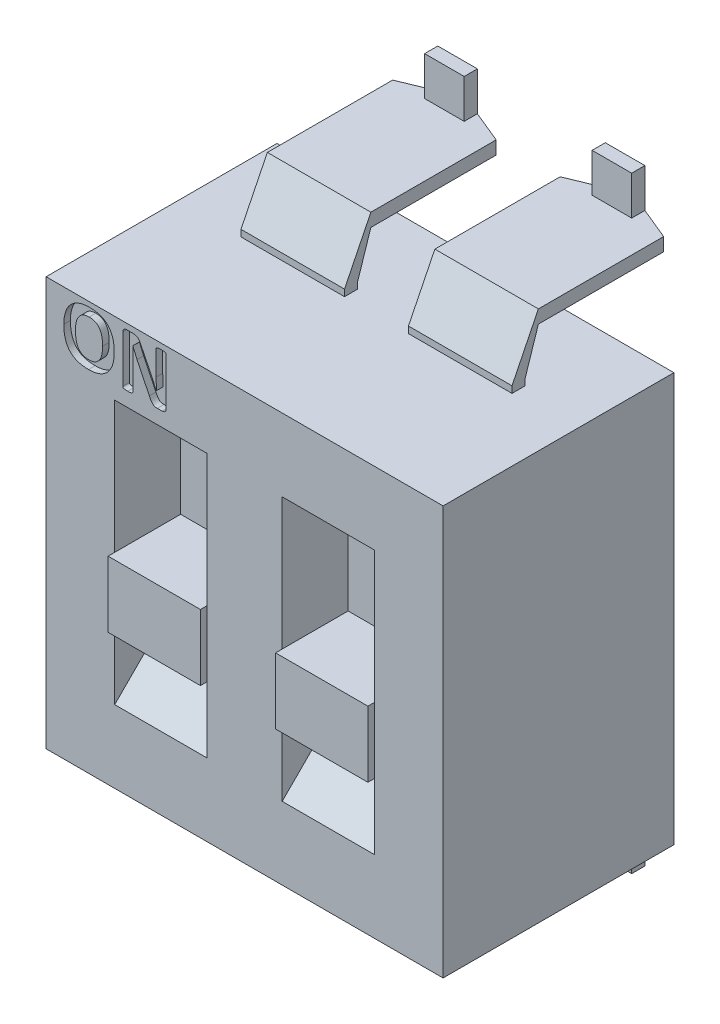
SolidWorks part; units mm, degrees
other "Детальный элемент1"
ref_plane "Спереди" through (0, 0, 0) normal (0, 0, 1) x (1, 0, 0)
ref_plane "Сверху" through (0, 0, 0) normal (0, 1, 0) x (1, 0, 0)
ref_plane "Справа" through (0, 0, 0) normal (1, 0, 0) x (0, 0, -1)
ref_plane "Плоскость1" through (0, 0, 1) normal (0, 0, 1) x (1, 0, 0)
sketch "Эскиз1" plane through (0, 0, 1) normal (0, 0, 1) x (1, 0, 0)
  line L1 (-3.01, -3.1) -> (3.01, -3.1)
  line L2 (-3.01, -3.1) -> (-3.01, 3.1)
  line L3 (-3.01, 3.1) -> (3.01, 3.1)
  line L4 (3.01, -3.1) -> (3.01, 3.1)
  line L5 (-3.01, -3.1) -> (3.01, 3.1) construction
  line L6 (-3.01, 3.1) -> (3.01, -3.1) construction
  point P0 (0, 0)
  dimension "D1" = 6.2
  dimension "D2" = 6.02
extrude "Бобышка-Вытянуть1" add sketch "Эскиз1" along normal blind 3.5
sketch "Эскиз2" plane through (0, -3.1, 0) normal (0, -1, 0) x (1, 0, 0)
  line L0 (-3.01, 1) -> (3.01, 1) construction
  line L1 (-2.055, 2.5) -> (-0.485, 2.5)
  line L2 (-2.055, 2.5) -> (-2.055, 2.3)
  line L3 (-2.055, 2.3) -> (-0.485, 2.3)
  line L4 (-0.485, 2.5) -> (-0.485, 2.3)
  line L5 (-2.055, 2.5) -> (-0.485, 2.3) construction
  line L6 (-2.055, 2.3) -> (-0.485, 2.5) construction
  line L7 (-3.01, 4.5) -> (-3.01, 1) construction
  point P0 (-1.27, 2.4)
  dimension "D1" = 1.57
  dimension "D2" = 0.2
  dimension "D3" = 1.4
  dimension "D4" = 1.74
extrude "Бобышка-Вытянуть2" add sketch "Эскиз2" along normal blind 0.1 separate body
sketch "Эскиз3" plane through (0, 0, 0) normal (0, 0, 1) x (1, 0, 0)
  line L1 (-1.57, -3.81) -> (-0.97, -3.81)
  line L2 (-1.57, -3.81) -> (-1.57, -4.6)
  line L3 (-1.57, -4.6) -> (-0.97, -4.6)
  line L4 (-0.97, -3.81) -> (-0.97, -4.6)
  line L5 (-1.57, -3.81) -> (-0.97, -4.6) construction
  line L6 (-1.57, -4.6) -> (-0.97, -3.81) construction
  point P0 (-1.27, -4.205)
  dimension "D1" = 0.6
  dimension "D2" = 0.79
  dimension "D3" = 4.6
extrude "Бобышка-Вытянуть3" add sketch "Эскиз3" along normal blind 0.2 separate body
sketch "Эскиз4" plane through (0, 0, 0.2) normal (0, 0, 1) x (1, 0, 0)
  line L0 (-0.97, -3.81) -> (-1.57, -3.81) construction
  line L1 (-2.055, -3.81) -> (-0.485, -3.81)
  line L2 (-2.055, -3.81) -> (-2.055, -4.01)
  line L3 (-2.055, -4.01) -> (-0.485, -4.01)
  line L4 (-0.485, -3.81) -> (-0.485, -4.01)
  dimension "D1" = 0.2
extrude "Бобышка-Вытянуть4" add sketch "Эскиз4" along normal offset from surface (1.9 mm away) 0.2 up to face at (-1.27, -3.15, 2.3)
chamfer "Фаска1" distance 0.2 distance2 0.485 2 edges at (-0.97, -3.91, 0.2) (-1.57, -3.91, 0.2) first distance on face at (-0.97, -4.166, 0.12) first distance on face at (-1.57, -4.166, 0.12)
loft "По сечениям1" add section face at (-1.27, -3.2, 2.4) section face at (-1.27, -3.91, 2.1) connector at (-2.055, -3.2, 2.5) connector at (-2.055, -4.01, 2.1)
sketch "Эскиз5" plane through (0, 0, 4.5) normal (0, 0, 1) x (1, 0, 0)
  line L5 (-1.97, 1) -> (-0.57, 1)
  line L6 (-1.97, 1) -> (-1.97, -1)
  line L7 (-1.97, -1) -> (-0.57, -1)
  line L8 (-0.57, 1) -> (-0.57, -1)
  line L9 (-1.97, 1) -> (-0.57, -1) construction
  line L10 (-1.97, -1) -> (-0.57, 1) construction
  point P0 (-1.27, 0)
  dimension "D1" = 2
  dimension "D2" = 1.4
extrude "Вырез-Вытянуть1" cut sketch "Эскиз5" against normal blind 1
chamfer "Фаска2" distance 1 angle 45 2 edges at (-1.27, 1, 4.5) (-1.27, -1, 4.5)
sketch "Эскиз6" plane through (0, 0, 3.5) normal (0, 0, 1) x (1, 0, 0)
  line L0 (-0.57, -1) -> (-0.57, 1) construction
  line L1 (-1.97, -1) -> (-0.57, -1)
  line L2 (-1.97, -1) -> (-1.97, 0)
  line L3 (-1.97, 0) -> (-0.57, 0)
  line L4 (-0.57, -1) -> (-0.57, 0)
  dimension "D1" = 1
extrude "Бобышка-Вытянуть5" add sketch "Эскиз6" along normal blind 1.1 separate body
mirror "Зеркальное отражение1" about plane through (0, 0, 0) normal (0, 1, 0) of bodies 111
pattern_linear "Линейный массив3" count 2 spacing 2.54 along (1, 0, 0) of "Вырез-Вытянуть1", "Фаска2"
pattern_linear "Линейный массив1" count 2 spacing 2.54 along (1, 0, 0) of bodies 120 111 113
sketch "Эскиз7" plane through (0, 0, 4.5) normal (0, 0, 1) x (1, 0, 0)
  text T0 "ON" font "Calibri" height 0.8
extrude "Вырез-Вытянуть2" cut sketch "Эскиз7" against normal blind 0.1
equation "\"N\"= 2"
equation "\"D2@Эскиз1\"=\"N\"*2.54+0.94"
equation "\"D1@Линейный массив1\"=\"N\""
equation "\"D1@Линейный массив2\"=\"N\""
equation "\"D1@Линейный массив3\"=\"N\""
